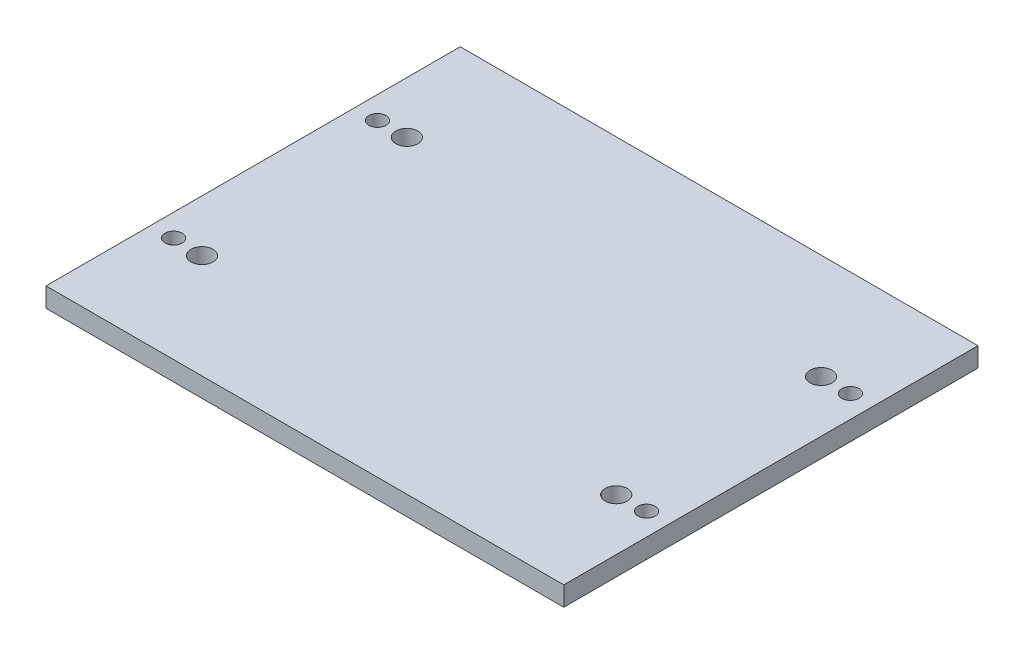
SolidWorks part; units mm, degrees
other "Markup1"
sketch "Sketch18" [suppressed] plane through (-63.5, -7.9375, -30) normal (-0.3676, -0.7619, -0.5334) x (0.8094, 0.0203, -0.5869)
ref_plane "Front Plane" through (0, 0, 0) normal (0, 0, 1) x (1, 0, 0)
ref_plane "Top Plane" through (0, 0, 0) normal (0, 1, 0) x (1, 0, 0)
ref_plane "Right Plane" through (0, 0, 0) normal (1, 0, 0) x (0, 0, -1)
sketch "Sketch1" plane through (0, 0, 0) normal (0, 1, 0) x (1, 0, 0)
  line L1 (-63.5, -50.8) -> (63.5, -50.8)
  line L2 (-63.5, -50.8) -> (-63.5, 50.8)
  line L3 (-63.5, 50.8) -> (63.5, 50.8)
  line L4 (63.5, -50.8) -> (63.5, 50.8)
  line L5 (-63.5, -50.8) -> (63.5, 50.8) construction
  line L6 (-63.5, 50.8) -> (63.5, -50.8) construction
  line L7 (58, 25) -> (-58, 25) construction
  line L8 (58, 25) -> (58, -25) construction
  line L9 (58, -25) -> (-58, -25) construction
  line L10 (-58, 25) -> (-58, -25) construction
  line L11 (58, 25) -> (-58, -25) construction
  line L12 (58, -25) -> (-58, 25) construction
  circle A0 centre (-58, 25) radius 2.75
  circle A1 centre (-58, -25) radius 2.75
  circle A2 centre (58, -25) radius 2.75
  circle A3 centre (58, 25) radius 2.75
  point P0 (0, 0)
  point P5 (0, 0)
  dimension "D5" = 5.5
  dimension "D1" = 101.6
  dimension "D2" = 127
  dimension "D3" = 50
  dimension "D4" = 116
extrude "Boss-Extrude1" add sketch "Sketch1" along normal blind 4.7625 contours A0 | L1 L4 L3 L2 A3 A2 A1 A0 | A1 | A2 | A3 region at (0, 0, 0) region at (-58, 0, -25) region at (-58, 0, 25) region at (58, 0, 25) region at (58, 0, -25)
sketch "Sketch2" plane through (0, 0, 0) normal (0, 1, 0) x (1, 0, 0)
  line L1 (-37.2297, 10.3476) -> (-31.88, -50.8)
  line L6 (37.2297, 10.3476) -> (31.88, -50.8)
  line L7 (-63.5, -50.8) -> (63.5, -50.8) construction
  line L11 (8.89, 41.275) -> (-8.89, 41.275)
  line L14 (-63.5, 50.8) -> (63.5, 50.8) construction
  arc A2 (37.2297, 10.3476) -> (8.89, 41.275) centre (8.89, 12.827) ccw
  arc A3 (-8.89, 41.275) -> (-37.2297, 10.3476) centre (-8.89, 12.827) ccw
  point P17 (0, 41.275)
  dimension "D1" = 9.525
  dimension "D2" = 28.448
  dimension "D3" = 95
  dimension "D4" = 17.78
sketch "Sketch7" plane through (0, 4.7625, 0) normal (0, 1, 0) x (1, 0, 0)
  point P0 (-58, 25)
  point P3 (58, 25)
  point P6 (58, -25)
  point P9 (-58, -25)
hole_wizard "M5x0.8 Tapped Hole1" positions "Sketch7" profile "Sketch8" tap size "M5x0.8" standard "ANSI Metric" end condition through all
sketch "Sketch8" plane through (-58, 4.7625, -25) normal (1, 0, 0) x (0, 0, 1)
  line L0 (0, 0) -> (0, 4.7625)
  line L1 (0, 4.7625) -> (2.1, 4.7625)
  line L2 (2.1, 4.7625) -> (2.1, 0)
  line L5 (2.1, 0) -> (0, 0)
  line L11 (0, -6.35) -> (0, 107.95) construction
  dimension "Thru Tap Drill Dia." = 4.2
  dimension "Thru Tap Drill Depth" = 4.7625
cosmetic thread "Hole Thread1" parameters "D2"=5
cosmetic thread "Hole Thread2" parameters "D2"=5
cosmetic thread "Hole Thread3" parameters "D2"=5
cosmetic thread "Hole Thread4" parameters "D2"=5
sketch "Sketch11" plane through (0, 0, 0) normal (0, -1, 0) x (-1, 0, 0)
  line L0 (0, 50.8) -> (0, -50.8) construction
  line L1 (63.5, 50.8) -> (-63.5, 50.8) construction
  line L2 (63.5, -50.8) -> (-63.5, -50.8) construction
  point P0 (-50.8, 25)
  point P2 (50.8, 25)
  point P4 (50.8, -25.2375)
  point P6 (-50.8, -25.2375)
  dimension "D1" = 101.6
  dimension "D2" = 50.2375
hole_wizard "1/4-28 Tapped Hole1" positions "Sketch11" profile "Sketch12" tap size "1/4-28" standard "ANSI Inch" end condition through all
sketch "Sketch12" plane through (50.8, 0, -25) normal (1, 0, 0) x (0, 0, -1)
  line L0 (0, 0) -> (0, 4.7625)
  line L1 (0, 4.7625) -> (2.7051, 4.7625)
  line L2 (2.7051, 4.7625) -> (2.7051, 0)
  line L5 (2.7051, 0) -> (0, 0)
  line L11 (0, -6.35) -> (0, 107.95) construction
  dimension "Thru Tap Drill Dia." = 5.4102
  dimension "Thru Tap Drill Depth" = 4.7625
cosmetic thread "Hole Thread5" parameters "D2"=6.35
cosmetic thread "Hole Thread6" parameters "D2"=6.35
cosmetic thread "Hole Thread7" parameters "D2"=6.35
cosmetic thread "Hole Thread8" parameters "D2"=6.35
sketch "Sketch19" [suppressed] plane through (0, 0, 0) normal (0, -1, 0) x (1, 0, 0)
  circle A0 centre (-50.8, 25.2375) radius 3.2639
  circle A1 centre (50.8, 25.2375) radius 3.2639
  circle A2 centre (50.8, -25) radius 3.2639
  circle A3 centre (-50.8, -25) radius 3.2639
  dimension "D1" = 6.5278
extrude "Cut-Extrude5" [suppressed] cut sketch "Sketch19" against normal through all
sketch "Sketch26" [suppressed] plane through (0, 0, 50.8) normal (0, 0, 1) x (1, 0, 0)
  line L0 (27.1175, 0) -> (36.6425, 0)
  line L2 (36.6425, 0) -> (36.6425, 1.5875)
  line L3 (27.1175, 1.5875) -> (27.1175, 0)
  line L4 (-63.5, 0) -> (63.5, 0) construction
  arc A0 (36.6425, 1.5875) -> (27.1175, 1.5875) centre (31.88, 1.5875) ccw
  point P9 (31.88, 0)
  dimension "D3" = 4.7625
  dimension "D2" = 1.5875
sweep "Cut-Sweep9" [suppressed] cut profiles "Sketch26" path "Sketch2"
sketch "Sketch27" [suppressed] plane through (0, 0, 0) normal (0, -1, 0) x (1, 0, 0)
  line L0 (-23.293, 50.8) -> (-28.7079, -11.0932)
  line L1 (-27.1175, 50.8) -> (27.1175, 50.8) construction
  line L2 (-8.89, -32.7206) -> (8.89, -32.7206)
  line L3 (28.7079, -11.0932) -> (23.293, 50.8)
  line L5 (-23.293, 50.8) -> (23.293, 50.8)
  line L6 (40.4671, 50.8) -> (41.8919, 34.5138)
  line L7 (36.6425, 50.8) -> (63.5, 50.8) construction
  line L9 (-63.5, -50.8) -> (63.5, -50.8) construction
  line L10 (36.6425, 50.8) -> (41.9922, -10.3476) construction
  line L11 (-40.4671, 50.8) -> (-41.8919, 34.5138)
  line L12 (-63.5, 50.8) -> (-36.6425, 50.8) construction
  line L14 (-63.5, -50.8) -> (63.5, -50.8) construction
  line L15 (-41.9199, -9.5206) -> (-36.6425, 50.8) construction
  line L16 (-40.4671, 50.8) -> (-63.5, 50.8)
  line L17 (-63.5, 50.8) -> (-63.5, -50.8)
  line L18 (-63.5, -50.8) -> (-8.89, -50.8)
  line L19 (8.89, -50.8) -> (63.5, -50.8)
  line L20 (63.5, -50.8) -> (63.5, 50.8)
  line L21 (63.5, 50.8) -> (40.4671, 50.8)
  line L22 (27.1175, 50.8) -> (32.4672, -10.3476) construction
  line L23 (-37.2297, -10.3476) -> (-31.88, 50.8) construction
  line L24 (-43.6381, 14.5552) -> (-45.7516, -9.602)
  line L25 (43.6381, 14.5552) -> (45.7516, -9.602)
  arc A0 (-28.7079, -11.0932) -> (-8.89, -32.7206) centre (-8.89, -12.827) ccw
  arc A1 (8.89, -32.7206) -> (28.7079, -11.0932) centre (8.89, -12.827) ccw
  arc A2 (-37.2297, -10.3476) -> (-8.89, -41.275) centre (-8.89, -12.827) ccw construction
  arc A3 (8.89, -41.275) -> (37.2297, -10.3476) centre (8.89, -12.827) ccw construction
  arc A4 (41.8919, 34.5138) -> (47.4771, 31.4824) centre (45.6874, 34.8459) ccw
  arc A5 (47.4771, 31.4824) -> (48.612, 18.5105) centre (50.8, 25.2375) cw
  arc A6 (48.612, 18.5105) -> (43.6381, 14.5552) centre (47.4336, 14.8873) ccw
  arc A7 (45.8722, -14.0481) -> (50.0722, -17.9636) centre (49.6801, -14.1739) ccw
  arc A8 (50.0722, -17.9636) -> (46.9301, -30.9215) centre (50.8, -25) cw
  arc A9 (46.9301, -30.9215) -> (41.5671, -32.17) centre (44.8458, -34.1108) ccw
  arc A10 (41.5671, -32.17) -> (8.89, -50.8) centre (8.89, -12.827) cw
  circle A11 centre (50.8, -25) radius 3.2639 construction
  circle A12 centre (50.8, 25.2375) radius 3.2639 construction
  arc A14 (8.4749, -46.0194) -> (41.9922, -10.3476) centre (8.89, -12.827) ccw construction
  arc A15 (-41.8919, 34.5138) -> (-47.4771, 31.4824) centre (-45.6874, 34.8459) cw
  arc A16 (-47.4771, 31.4824) -> (-48.612, 18.5105) centre (-50.8, 25.2375) ccw
  arc A17 (-48.612, 18.5105) -> (-43.6381, 14.5552) centre (-47.4336, 14.8873) cw
  arc A18 (-45.8722, -14.0481) -> (-50.0722, -17.9636) centre (-49.6801, -14.1739) cw
  arc A19 (-50.0722, -17.9636) -> (-46.9301, -30.9215) centre (-50.8, -25) ccw
  arc A20 (-46.9301, -30.9215) -> (-41.5671, -32.17) centre (-44.8458, -34.1108) cw
  arc A21 (-41.5671, -32.17) -> (-8.89, -50.8) centre (-8.89, -12.827) ccw
  circle A22 centre (-50.8, -25) radius 3.2639 construction
  circle A23 centre (-50.8, 25.2375) radius 3.2639 construction
  arc A24 (-41.9199, -9.5206) -> (-9.3051, -46.0194) centre (-8.89, -12.827) ccw construction
  arc A25 (-45.7516, -9.602) -> (-45.8722, -14.0481) centre (-8.89, -12.827) ccw
  arc A26 (45.7516, -9.602) -> (45.8722, -14.0481) centre (8.89, -12.827) cw
  dimension "D4" = 3.81
  dimension "D2" = 3.81
  dimension "D3" = 3.81
  dimension "D5" = 3.81
  dimension "D6" = 3.81
  dimension "D7" = 3.81
  dimension "D8" = 3.81
  dimension "D1" = 3.81
extrude "Cut-Extrude6" [suppressed] cut sketch "Sketch27" against normal blind 6.35
sketch "Sketch28" [suppressed] plane through (0, 0, 0) normal (0, -1, 0) x (-1, 0, 0)
  line L0 (41.8919, -34.5138) -> (43.6381, -14.5552)
  line L1 (-41.8919, -34.5138) -> (-43.6381, -14.5552)
  arc A0 (45.8722, 14.0481) -> (41.5671, 32.17) centre (-0.9264, 12.5029) ccw
  arc A1 (46.9301, 30.9215) -> (41.5671, 32.17) centre (44.8458, 34.1108) cw
  arc A2 (45.7516, 9.602) -> (45.8722, 14.0481) centre (8.89, 12.827) ccw construction
  arc A3 (45.8722, 14.0481) -> (50.0722, 17.9636) centre (49.6801, 14.1739) cw
  arc A4 (50.0722, 17.9636) -> (45.8722, 14.0481) centre (49.6801, 14.1739) ccw construction
  arc A5 (50.0722, 17.9636) -> (46.9301, 30.9215) centre (50.8, 25) ccw
  arc A6 (47.4771, -31.4824) -> (48.612, -18.5105) centre (50.8, -25.2375) ccw
  arc A7 (48.612, -18.5105) -> (43.6381, -14.5552) centre (47.4336, -14.8873) cw
  arc A8 (47.4771, -31.4824) -> (41.8919, -34.5138) centre (45.6874, -34.8459) ccw
  arc A9 (-41.8919, -34.5138) -> (-47.4771, -31.4824) centre (-45.6874, -34.8459) ccw
  arc A10 (-43.6381, -14.5552) -> (-48.612, -18.5105) centre (-47.4336, -14.8873) cw
  arc A11 (-45.8722, 14.0481) -> (-50.0722, 17.9636) centre (-49.6801, 14.1739) ccw
  arc A12 (-41.5671, 32.17) -> (-46.9301, 30.9215) centre (-44.8458, 34.1108) cw
  arc A13 (-46.9301, 30.9215) -> (-50.0722, 17.9636) centre (-50.8, 25) ccw
  arc A14 (-48.612, -18.5105) -> (-47.4771, -31.4824) centre (-50.8, -25.2375) ccw
  arc A15 (47.4771, -31.4824) -> (48.612, -18.5105) centre (50.8, -25.2375) ccw construction
  arc A16 (-48.612, -18.5105) -> (-47.4771, -31.4824) centre (-50.8, -25.2375) ccw construction
  arc A17 (-46.9301, 30.9215) -> (-50.0722, 17.9636) centre (-50.8, 25) ccw construction
  arc A18 (-45.8722, 14.0481) -> (-41.5671, 32.17) centre (0.9264, 12.5029) cw
  arc A19 (-8.89, 41.275) -> (-37.2297, 10.3476) centre (-8.89, 12.827) ccw construction
  arc A20 (-45.8722, 14.0481) -> (-45.7516, 9.602) centre (-8.89, 12.827) ccw construction
  dimension "D1" = 28.1978
extrude "Cut-Extrude7" [suppressed] cut sketch "Sketch28" against normal blind 3.175
fillet "Fillet1" [suppressed] radius 3.048
fillet "Fillet2" [suppressed] radius 3.175
equation "\"D3@Sketch27\"=\"D2@Sketch27\""
equation "\"D5@Sketch27\"=\"D2@Sketch27\""
equation "\"D4@Sketch27\"=\"D2@Sketch27\""
equation "\"D6@Sketch27\"=\"D2@Sketch27\""
equation "\"D7@Sketch27\"=\"D2@Sketch27\""
equation "\"D8@Sketch27\"=\"D2@Sketch27\""
equation "\"D1@Sketch27\"=\"D2@Sketch27\""
